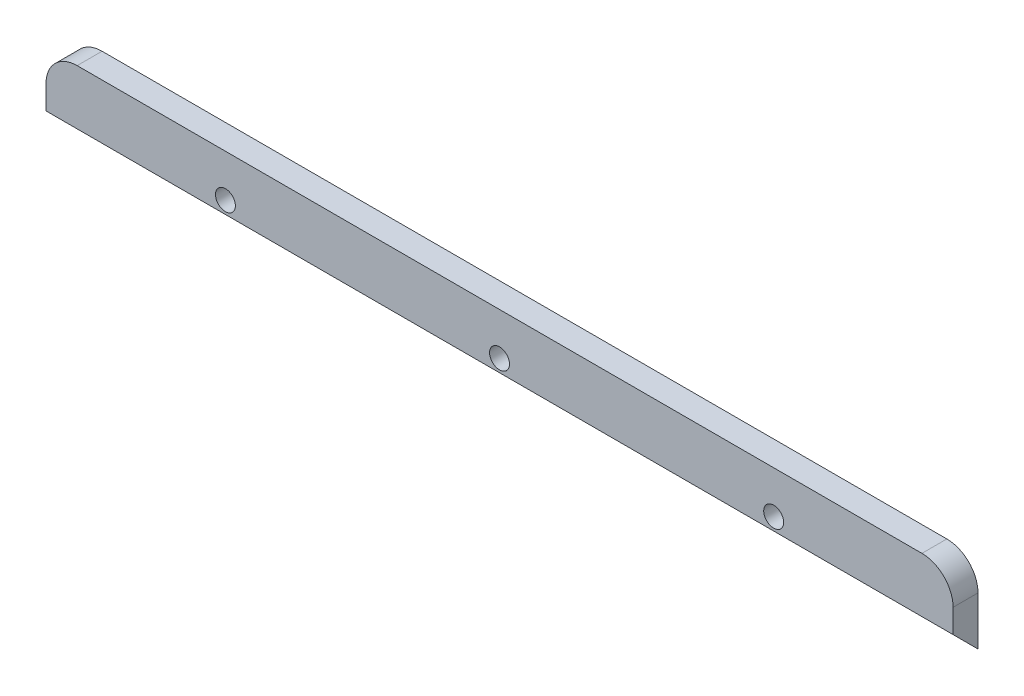
SolidWorks part; units mm, degrees
material "6061-T6 (SS)"
ref_plane "Front Plane" through (0, 0, 0) normal (0, 0, 1) x (1, 0, 0)
ref_plane "Top Plane" through (0, 0, 0) normal (0, 1, 0) x (1, 0, 0)
ref_plane "Right Plane" through (0, 0, 0) normal (1, 0, 0) x (0, 0, -1)
sketch "Sketch1" plane through (0, 0, 0) normal (1, 0, 0) x (0, 0, -1)
  line L0 (-3.0983, 0) -> (1.226, 0) construction
  line L1 (0, -3.2) -> (-2, -1.2)
  line L2 (0, -3.2) -> (0, 3.2)
  line L4 (-2, -1.2) -> (-2, 3.2)
  line L5 (-2, 3.2) -> (0, 3.2)
  dimension "D1" = 2
  dimension "D2" = 45
  dimension "D3" = 6.4
extrude "Boss-Extrude1" add sketch "Sketch1" along normal mid plane 72.8
sketch "Sketch4" [suppressed] plane through (0, 0, 0) normal (0, 0, 1) x (1, 0, 0)
  line L1 (7.5, 1.5) -> (-7.5, 1.5)
  line L2 (7.5, 1.5) -> (7.5, -3.2)
  line L3 (7.5, -3.2) -> (-7.5, -3.2)
  line L4 (-7.5, 1.5) -> (-7.5, -3.2)
  line L5 (0, 7.7759) -> (0, -8.8374) construction
  line L8 (-7.5, -1.7) -> (-7.5, -0.7) construction
  dimension "D1" = 4.7
hole_wizard "M2x0.4 Tapped Hole1" positions "Sketch2" profile "Sketch3" tap size "M2x0.4" standard "ANSI Metric" end condition through all
sketch "Sketch2" plane through (0, 0, 2) normal (0, 0, 1) x (1, 0, 0)
  circle A0 centre (-22, -0.2) radius 1.2
  circle A1 centre (-22, -0.2) radius 1.2 construction
  circle A2 centre (22, -0.2) radius 1.2
  circle A3 centre (22, -0.2) radius 1.2 construction
  point P0 (22, -0.2)
  point P2 (0, -0.2)
  point P5 (-22, -0.2)
sketch "Sketch3" plane through (22, -0.2, 2) normal (1, 0, 0) x (0, -1, 0)
  line L0 (0, 0) -> (0, 2)
  line L1 (0, 2) -> (0.8, 2)
  line L2 (0.8, 2) -> (0.8, 0)
  line L5 (0.8, 0) -> (0, 0)
  line L11 (0, -6.35) -> (0, 107.95) construction
  dimension "Thru Tap Drill Dia." = 1.6
  dimension "Thru Tap Drill Depth" = 2
cosmetic thread "Hole Thread1"
cosmetic thread "Hole Thread2"
cosmetic thread "Hole Thread3"
extrude "Cut-Extrude4" [suppressed] cut sketch "Sketch4" along normal through all
fillet "Fillet3" radius 2.5 2 edges at (-36.4, 3.2, 1) (36.4, 3.2, 1)
